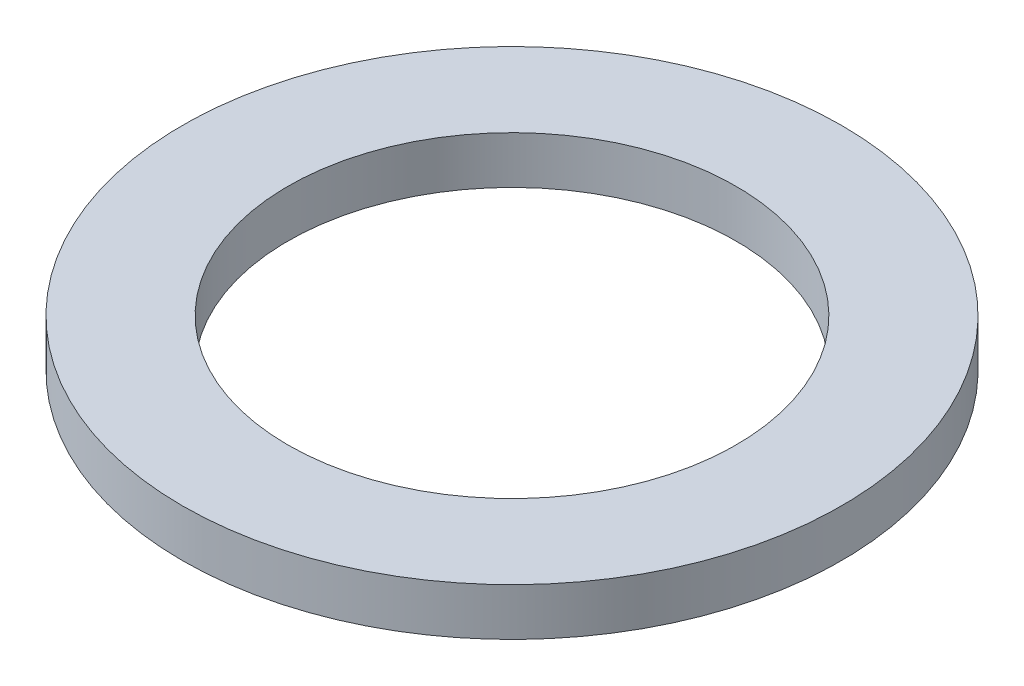
SolidWorks part; units mm, degrees
ref_plane "Front Plane" through (0, 0, 0) normal (0, 0, 1) x (1, 0, 0)
ref_plane "Top Plane" through (0, 0, 0) normal (0, 1, 0) x (1, 0, 0)
ref_plane "Right Plane" through (0, 0, 0) normal (1, 0, 0) x (0, 0, -1)
sketch "Sketch1" plane through (0, 0, 0) normal (0, 1, 0) x (1, 0, 0)
  circle A0 centre (0, 0) radius 62.5
  dimension "FLANGE_OD" = 125
extrude "Boss-Extrude1" add sketch "Sketch1" along normal blind 9
sketch "Sketch2" plane through (0, 0, 0) normal (0, 1, 0) x (1, 0, 0)
  circle A0 centre (0, 0) radius 42.5
  dimension "BORE_D" = 85
extrude "Cut-Extrude1" cut sketch "Sketch2" along normal through all
sketch "Sketch3" plane through (0, 9, 0) normal (0, 1, 0) x (1, 0, 0)
  circle A0 centre (0, 0) radius 24.4679 construction
  circle A1 centre (-24.4679, 0) radius 3.0769
  dimension "BOLT_D" = 6.1538
  dimension "BOLT_PCD" = 48.9358
extrude "Cut-Extrude2" cut sketch "Sketch3" against normal blind 5.5272 rebuild error yes
pattern_circular "CirPattern1" count 5 over 360 rebuild error yes
